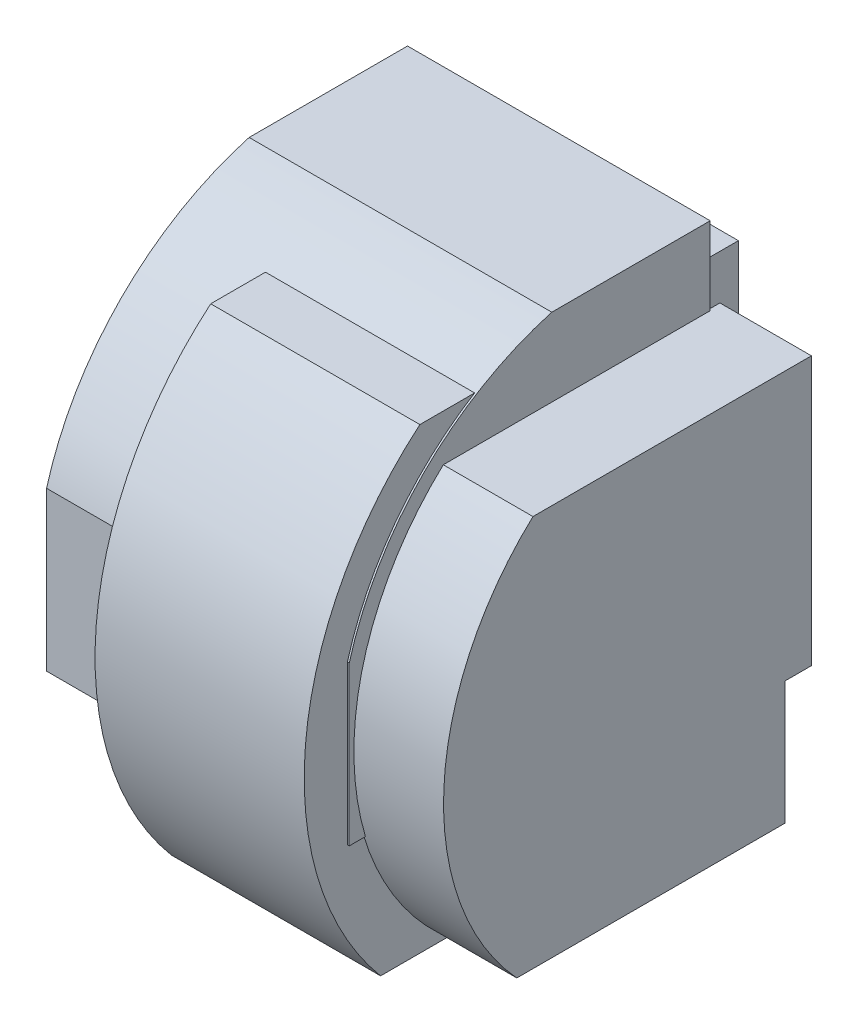
SolidWorks part; units mm, degrees
ref_plane "Front Plane" through (0, 0, 0) normal (0, 0, 1) x (1, 0, 0)
ref_plane "Top Plane" through (0, 0, 0) normal (0, 1, 0) x (1, 0, 0)
ref_plane "Right Plane" through (0, 0, 0) normal (1, 0, 0) x (0, 0, -1)
sketch "Sketch2" plane through (9.0434, 0, 0) normal (-1, 0, 0) x (0, 0, 1)
  line B0 (21.5519, 6.0579) -> (-10.8966, 6.0579)
  line B1 (21.5519, 6.0579) -> (21.5519, -6.0579)
  line B2 (21.5519, -6.0579) -> (-10.8966, -6.0579)
  line B3 (-10.8966, 6.0579) -> (-10.8966, -6.0579)
  line B4 (-6.0579, 21.5519) -> (-6.0579, -10.8966)
  line B5 (-6.0579, 21.5519) -> (6.0579, 21.5519)
  line B6 (6.0579, 21.5519) -> (6.0579, -10.8966)
  line B7 (-6.0579, -10.8966) -> (6.0579, -10.8966)
sketch_block_instance "Block1-1"
sketch_block "Block1"
sketch_block_instance "Block1-2"
sketch "Sketch3" plane through (9.0434, 0, 0) normal (-1, 0, 0) x (0, 0, 1)
  line L1 (-6.0579, 21.5519) -> (-6.0579, -10.8966) construction
  line L3 (-6.0579, 21.5519) -> (-6.0579, 6.0579)
  line L4 (-6.0579, 21.5519) -> (6.0579, 21.5519) construction
  line L5 (-6.0579, 21.5519) -> (6.0579, 21.5519)
  line L6 (-6.0579, -10.8966) -> (6.0579, -10.8966) construction
  line L7 (-6.0579, -10.8966) -> (6.0579, -10.8966)
  line L8 (6.0579, 21.5519) -> (6.0579, -10.8966) construction
  line L9 (6.0579, -6.0579) -> (6.0579, -10.8966)
  line L10 (-6.0579, 6.0579) -> (-10.8966, 6.0579)
  line L11 (21.5519, 6.0579) -> (21.5519, -6.0579) construction
  line L12 (21.5519, -6.0579) -> (-10.8966, -6.0579) construction
  line L13 (21.5519, 6.0579) -> (21.5519, -6.0579)
  line L14 (21.5519, -6.0579) -> (6.0579, -6.0579)
  arc A0 (6.0579, 21.5519) -> (21.5519, 6.0579) centre (0, 0) cw
  arc A1 (-6.0579, -10.8966) -> (-10.8966, 6.0579) centre (0, 0) cw
extrude "Boss-Extrude1" add sketch "Sketch3" against normal up to surface (23.1521 mm away)
sketch "Sketch4" plane through (16.0538, 0, 0) normal (-1, 0, 0) x (0, 0, 1)
  line B0 (-8.3579, -16.0079) -> (19.0132, -16.0079)
  line B1 (-8.3579, -16.0079) -> (-8.3579, 8.3579)
  line B2 (-8.3579, 8.3579) -> (19.0132, 8.3579)
  line B3 (19.0132, -16.0079) -> (19.0132, 8.3579)
  line B4 (16.0079, -8.3579) -> (16.0079, 19.0132)
  line B5 (16.0079, -8.3579) -> (-8.3579, -8.3579)
  line B6 (-8.3579, -8.3579) -> (-8.3579, 19.0132)
  line B7 (16.0079, 19.0132) -> (-8.3579, 19.0132)
sketch_block_instance "Block2-1"
sketch_block "Block2"
sketch_block_instance "Block2-2"
sketch "Sketch5" plane through (16.0538, 0, 0) normal (-1, 0, 0) x (0, 0, 1)
  line L0 (16.0079, 19.0132) -> (-8.3579, 19.0132) construction
  line L1 (-8.3579, -8.3579) -> (-8.3579, 19.0132) construction
  line L2 (16.0079, 19.0132) -> (-8.3579, 19.0132)
  line L3 (-8.3579, -8.3579) -> (-8.3579, 19.0132)
  line L4 (-8.3579, -16.0079) -> (19.0132, -16.0079) construction
  line L6 (-8.3579, -16.0079) -> (19.0132, -16.0079)
  line L8 (-8.3579, -8.3579) -> (-8.3579, -16.0079)
  arc A1 (16.0079, 19.0132) -> (19.0132, -16.0079) centre (0, 0) cw
extrude "Boss-Extrude2" add sketch "Sketch5" against normal up to surface (16 mm away)
sketch "Sketch6" plane through (32.0538, 0, 0) normal (1, 0, 0) x (0, 0, -1)
  line B0 (-15.5926, -14.3579) -> (4.9374, -14.3579)
  line B1 (-15.5926, -14.3579) -> (-15.5926, 6.9421)
  line B2 (-15.5926, 6.9421) -> (4.9374, 6.9421)
  line B3 (4.9374, -14.3579) -> (4.9374, 6.9421)
  line B4 (3.5623, -3.0579) -> (-14.2177, -3.0579) construction
  line B5 (-14.357, 15.5935) -> (-14.3582, -4.9365)
  line B6 (-14.357, 15.5935) -> (6.943, 15.5922)
  line B7 (6.943, 15.5922) -> (6.9418, -4.9378)
  line B8 (-14.3582, -4.9365) -> (6.9418, -4.9378)
  line B9 (-3.0581, -3.5622) -> (-3.0571, 14.2178) construction
sketch_block_instance "Block3-1"
sketch_block "Block3" parameters "D1"=10
sketch_block_instance "Block3-2"
sketch "Sketch7" plane through (32.0538, 0, 0) normal (1, 0, 0) x (0, 0, -1)
  line L0 (-15.5926, -14.3579) -> (4.9374, -14.3579) construction
  line L1 (4.9374, -14.3579) -> (4.9374, 6.9421) construction
  line L2 (-14.3582, -4.9365) -> (6.9418, -4.9378) construction
  line L3 (6.943, 15.5922) -> (6.9418, -4.9378) construction
  line L4 (-14.357, 15.5935) -> (6.943, 15.5922) construction
  line L5 (-15.5926, -14.3579) -> (4.9374, -14.3579)
  line L6 (4.9374, -14.3579) -> (4.9374, -4.9376)
  line L7 (4.9374, -4.9376) -> (6.9418, -4.9378)
  line L8 (6.943, 15.5922) -> (6.9418, -4.9378)
  line L9 (-14.357, 15.5935) -> (6.943, 15.5922)
  arc A0 (-14.357, 15.5935) -> (-15.5926, -14.3579) centre (0, 0) ccw
extrude "Boss-Extrude3" add sketch "Sketch7" along normal up to surface (7 mm away)
